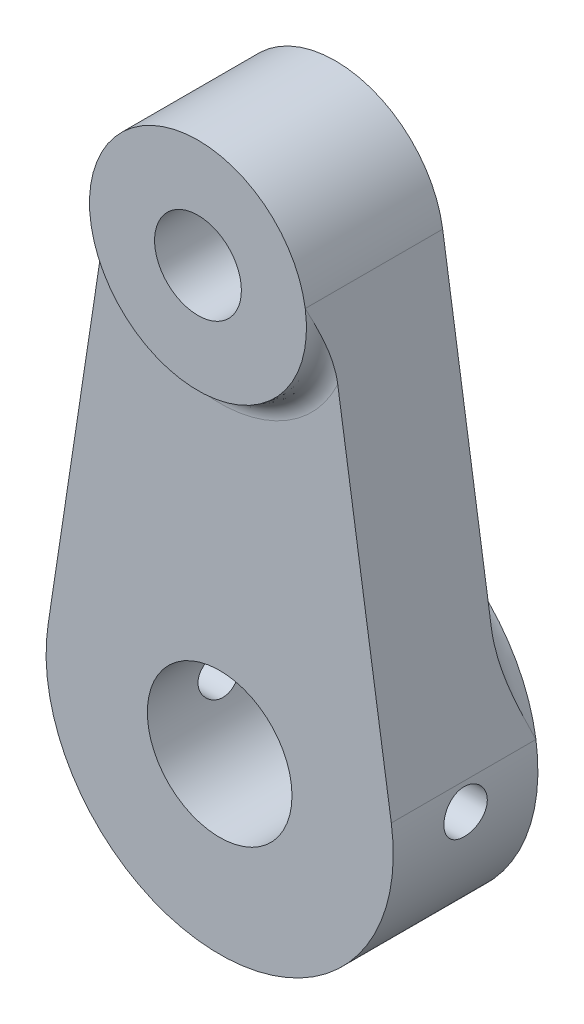
SolidWorks part; units mm, degrees
ref_plane "Front Plane" through (0, 0, 0) normal (0, 0, 1) x (1, 0, 0)
ref_plane "Top Plane" through (0, 0, 0) normal (0, 1, 0) x (1, 0, 0)
ref_plane "Right Plane" through (0, 0, 0) normal (1, 0, 0) x (0, 0, -1)
sketch "Sketch1" plane through (0, 0, 0) normal (0, 0, 1) x (1, 0, 0)
  circle A0 centre (0, 0) radius 7.5
  circle A1 centre (0, 0) radius 3
  dimension "D1" = 15
  dimension "D2" = 6
extrude "Boss-Extrude1" add sketch "Sketch1" along normal blind 9.5
sketch "Sketch2" plane through (0, 0, 0) normal (0, 0, 1) x (1, 0, 0)
  line L0 (-7.4151, 1.125) -> (-11.8642, -28.2)
  line L1 (0, 0) -> (0, -30) construction
  line L2 (7.4151, 1.125) -> (11.8642, -28.2)
  circle A0 centre (0, -30) radius 12
  circle A1 centre (0, -30) radius 5
  circle A2 centre (0, 0) radius 7.5 construction
  dimension "D1" = 10
  dimension "D2" = 24
  dimension "D3" = 30
extrude "Boss-Extrude2" add sketch "Sketch2" along normal blind 8 and the other way blind 2 separate body contours A0 A1 region at (-0.877, -41.6276, 0)
sketch "Sketch3" plane through (0, 0, 0) normal (0, 0, 1) x (1, 0, 0)
  line L0 (7.4151, 1.125) -> (11.8642, -28.2) construction
  line L1 (-7.4151, 1.125) -> (-11.8642, -28.2) construction
  line L2 (7.4151, 1.125) -> (11.8642, -28.2)
  line L3 (-7.4151, 1.125) -> (-11.8642, -28.2)
  circle A0 centre (0, -30) radius 12 construction
  circle A1 centre (0, 0) radius 7.5 construction
  arc A3 (11.8642, -28.2) -> (-11.8642, -28.2) centre (0, -30) ccw
  arc A5 (-7.4151, 1.125) -> (7.4151, 1.125) centre (0, 0) ccw
extrude "Boss-Extrude3" add sketch "Sketch3" along normal blind 8
sketch "Sketch4" plane through (0, 0, 0) normal (1, 0, 0) x (0, 0, -1)
  line L0 (-8, -28.2) -> (-8, -42) construction
  line L1 (-8, -42) -> (2, -42) construction
  circle A0 centre (-3, -30) radius 1.5
  dimension "D1" = 3
  dimension "D2" = 5
  dimension "D3" = 12
extrude "Cut-Extrude1" cut sketch "Sketch4" against normal through all both and the other way through all
fillet "Fillet1" radius 1.5 1 edges at (0, -7.5, 8)
fillet "Fillet2" radius 2 1 edges at (0, -18, 0)
